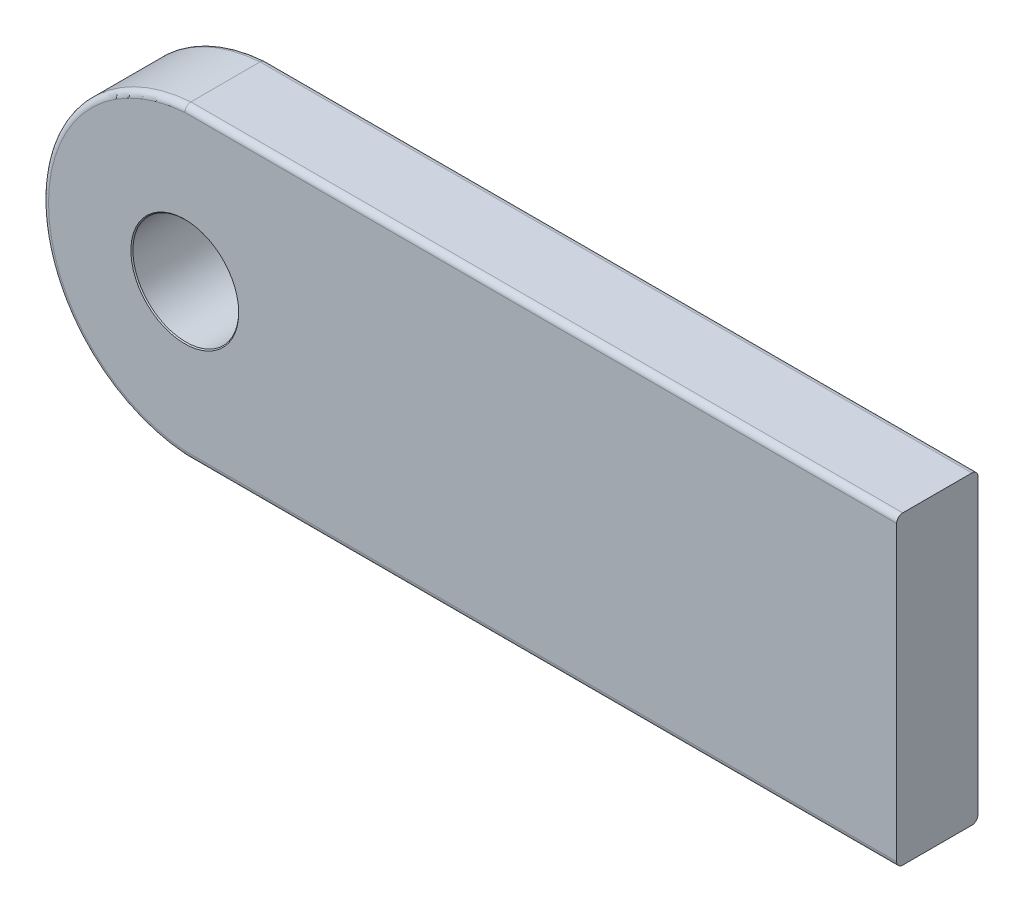
SolidWorks part; units mm, degrees
ref_plane "Front Plane" through (0, 0, 0) normal (0, 0, 1) x (1, 0, 0)
ref_plane "Top Plane" through (0, 0, 0) normal (0, 1, 0) x (1, 0, 0)
ref_plane "Right Plane" through (0, 0, 0) normal (1, 0, 0) x (0, 0, -1)
sketch "Sketch1" plane through (0, 0, 0) normal (0, 0, 1) x (1, 0, 0)
  line L0 (-208.7746, 0) -> (131.2254, 0) construction
  line L1 (-240.5263, 75) -> (109.4737, 75)
  line L3 (-240.5263, -75) -> (109.4737, -75)
  line L4 (109.4737, 75) -> (109.4737, 40)
  line L5 (109.4737, 40) -> (-20.5263, 40)
  line L10 (-20.5263, 40) -> (-20.5263, -40)
  line L11 (-20.5263, -40) -> (109.4737, -40)
  line L12 (109.4737, -40) -> (109.4737, -75)
  circle A1 centre (-240.5263, 0) radius 26
  arc A2 (-240.5263, 75) -> (-240.5263, -75) centre (-235.3477, 0) ccw
  dimension "D2" = 420
  dimension "D7" = 52
  dimension "D8" = 350
  dimension "D1" = 150
  dimension "D3" = 130
  dimension "D4" = 80
  dimension "D5" = 80
extrude "Boss-Extrude1" add sketch "Sketch1" along normal mid plane 40 contours L1 L4 L5 L10 L11 L12 L3 A2
sketch "Sketch2" plane through (0, 0, 20) normal (0, 0, 1) x (1, 0, 0)
  line L0 (0, 0) -> (-310.5263, 0) construction
  circle A0 centre (-240.5263, 0) radius 26
  arc A4 (-240.5263, 75) -> (-240.5263, -75) centre (-235.3477, 0) ccw construction
  dimension "D1" = 52
  dimension "D2" = 70
extrude "Cut-Extrude1" cut sketch "Sketch2" against normal blind 40
sketch "Sketch3" plane through (0, 0, 20) normal (0, 0, 1) x (1, 0, 0)
  line L0 (109.4737, -40) -> (109.4737, -75) construction
  line L1 (-45.5804, 57.7373) -> (109.4737, 57.7373)
  line L2 (-45.5804, 57.7373) -> (-45.5804, -62.07)
  line L3 (-45.5804, -62.07) -> (109.4737, -62.07)
  line L4 (109.4737, 57.7373) -> (109.4737, -62.07)
extrude "Boss-Extrude2" add sketch "Sketch3" against normal through all
fillet "Fillet1" radius 3 6 edges at (-65.5263, -75, -20) (-310.5263, 0, -20) (-65.5263, 75, -20) (-65.5263, -75, 20) (-310.5263, 0, 20) (-65.5263, 75, 20)
chamfer "Chamfer1" distance 0.5 angle 45 2 edges at (-214.5263, 0, 20) (-214.5263, 0, -20)
